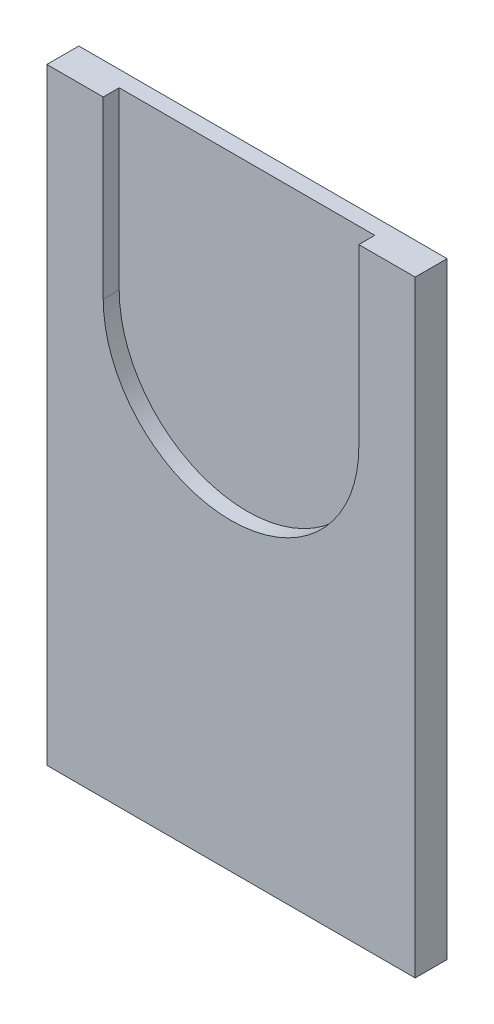
SolidWorks part; units mm, degrees
ref_plane "정면" through (0, 0, 0) normal (0, 0, 1) x (1, 0, 0)
ref_plane "윗면" through (0, 0, 0) normal (0, 1, 0) x (1, 0, 0)
ref_plane "우측면" through (0, 0, 0) normal (1, 0, 0) x (0, 0, -1)
sketch "스케치1" plane through (0, 0, 0) normal (0, 0, 1) x (1, 0, 0)
  line L1 (-28.82, 62.5) -> (28.82, 62.5)
  line L2 (-28.82, 62.5) -> (-28.82, -62.5)
  line L3 (-28.82, -62.5) -> (28.82, -62.5)
  line L4 (28.82, 62.5) -> (28.82, -62.5)
  line L5 (-28.82, 62.5) -> (28.82, -62.5) construction
  line L6 (-28.82, -62.5) -> (28.82, 62.5) construction
  point P0 (0, 0)
  dimension "D1" = 57.64
  dimension "D2" = 125
extrude "보스-돌출1" add sketch "스케치1" along normal blind 5
sketch "스케치2" plane through (0, 0, 5) normal (0, 0, 1) x (1, 0, 0)
  line L2 (20, 5.1017) -> (20, 62.5)
  line L3 (28.82, 62.5) -> (-28.82, 62.5) construction
  line L5 (-20, 62.5) -> (-20, 5.1017)
  line L6 (-20, 62.5) -> (20, 62.5)
  line L7 (-28.82, 62.5) -> (-28.82, -62.5) construction
  arc A19 (20, 5.1017) -> (-20, 5.1017) centre (0, 5.1017) cw
  point P3 (0, 62.5)
  dimension "D1" = 20
  dimension "D3" = 57.3983
  dimension "D2" = 28.82
extrude "컷-돌출1" cut sketch "스케치2" against normal blind 2.5
sketch "스케치3" plane through (0, 0, 5) normal (0, 0, 1) x (1, 0, 0)
  line L0 (28.82, -62.5) -> (28.82, 62.5) construction
  line L1 (-28.82, 62.5) -> (28.82, 62.5)
  line L2 (-28.82, 62.5) -> (-28.82, 32.5)
  line L3 (-28.82, 32.5) -> (28.82, 32.5)
  line L4 (28.82, 62.5) -> (28.82, 32.5)
  dimension "D1" = 30
extrude "컷-돌출2" cut sketch "스케치3" against normal blind 10
